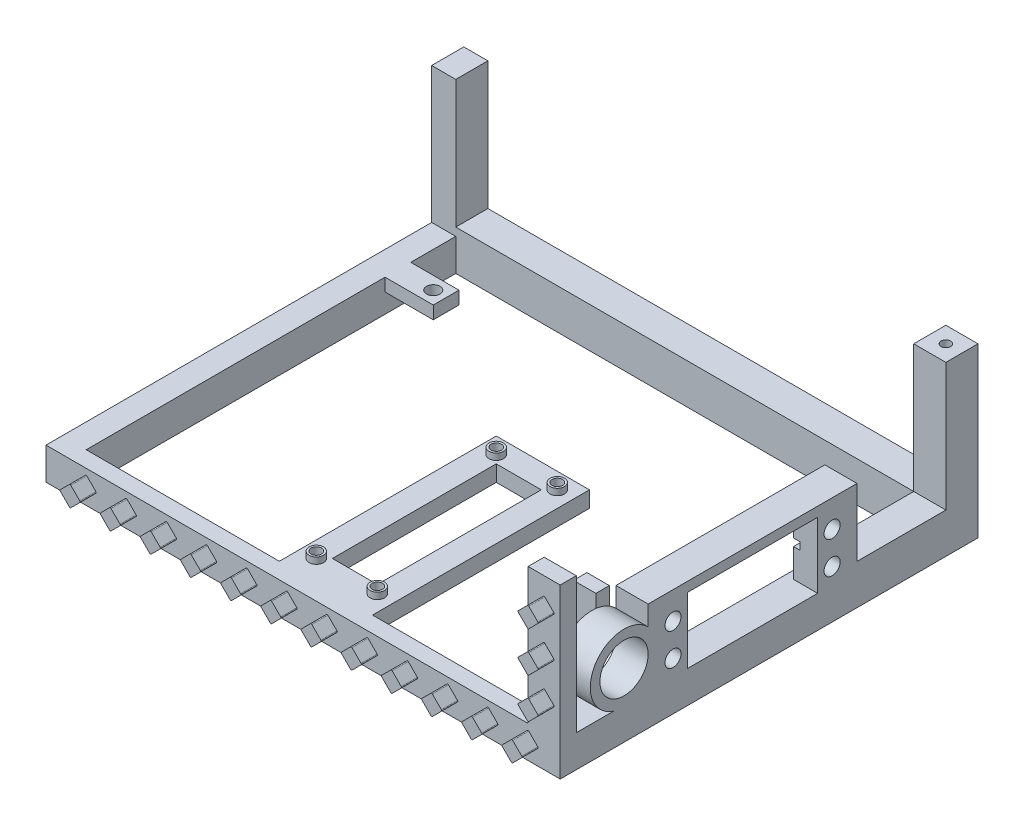
SolidWorks part; units mm, degrees
other "Markup1"
sketch "Sketch27" plane through (-85, 52.3, 65) normal (-0.8972, 0.4289, 0.105) x (0.3802, 0.6295, 0.6776)
ref_plane "Front Plane" through (0, 0, 0) normal (0, 0, 1) x (1, 0, 0)
ref_plane "Top Plane" through (0, 0, 0) normal (0, 1, 0) x (1, 0, 0)
ref_plane "Right Plane" through (0, 0, 0) normal (1, 0, 0) x (0, 0, -1)
sketch "Sketch1" plane through (0, 0, 0) normal (0, 1, 0) x (1, 0, 0)
  line L0 (0, 0) -> (0, 70) construction
  line L1 (-85, -60) -> (75, -60)
  line L2 (-85, -60) -> (-85, 70)
  line L3 (-85, 70) -> (75, 70)
  line L4 (75, -60) -> (75, 70)
  line L5 (0, 0) -> (0, -60) construction
  point P0 (0, 0)
  dimension "D1" = 160
  dimension "D2" = 70
  dimension "D3" = 60
extrude "Boss-Extrude1" add sketch "Sketch1" along normal blind 10
sketch "Sketch2" plane through (0, 10, 0) normal (0, 1, 0) x (1, 0, 0)
  line L0 (-85, 70) -> (75, 70)
  line L4 (-85, 70) -> (-85, 60)
  line L5 (-85, 70) -> (-85, -60) construction
  line L6 (-85, 60) -> (65, 60)
  line L13 (75, 70) -> (75, -60)
  line L14 (75, -60) -> (65, -60)
  line L15 (-85, -60) -> (75, -60) construction
  line L16 (65, -60) -> (65, 60)
extrude "Boss-Extrude2" add sketch "Sketch2" along normal blind 42.3
sketch "Sketch6" plane through (0, 0, 60) normal (0, 0, 1) x (1, 0, 0)
  line L0 (65, 10) -> (75, 10) construction
  line L1 (75, 52.3) -> (75, 0) construction
  line L2 (69.7879, 40.6121) -> (66.9621, 43.4379)
  line L79 (65, 10) -> (65, 0) construction
  line L156 (-85, 0) -> (75, 0) construction
  line L157 (66.9621, 43.8621) -> (69.7879, 46.6879)
  line L158 (70.2121, 46.6879) -> (73.0379, 43.8621)
  line L159 (70, 10) -> (70, 52.3) construction
  line L160 (65, 52.3) -> (75, 52.3) construction
  line L185 (65, 5) -> (-85, 5) construction
  line L186 (-85, 10) -> (-85, 0) construction
  line L187 (-10, 8.25) -> (-10, 1.75) construction
  line L188 (-10.2121, 8.0379) -> (-13.0379, 5.2121)
  line L189 (-13.0379, 4.7879) -> (-10.2121, 1.9621)
  line L190 (-9.7879, 1.9621) -> (-6.9621, 4.7879)
  line L191 (-6.9621, 5.2121) -> (-9.7879, 8.0379)
  line L192 (73.25, 31.15) -> (66.75, 31.15) construction
  line L193 (66.9621, 31.3621) -> (69.7879, 34.1879)
  line L194 (70.2121, 34.1879) -> (73.0379, 31.3621)
  line L195 (73.0379, 30.9379) -> (70.2121, 28.1121)
  line L196 (69.7879, 28.1121) -> (66.9621, 30.9379)
  line L197 (5.5379, 5.2121) -> (2.7121, 8.0379)
  line L198 (2.2879, 8.0379) -> (-0.5379, 5.2121)
  line L199 (-0.5379, 4.7879) -> (2.2879, 1.9621)
  line L200 (2.7121, 1.9621) -> (5.5379, 4.7879)
  line L201 (18.0379, 5.2121) -> (15.2121, 8.0379)
  line L202 (14.7879, 8.0379) -> (11.9621, 5.2121)
  line L203 (11.9621, 4.7879) -> (14.7879, 1.9621)
  line L204 (15.2121, 1.9621) -> (18.0379, 4.7879)
  line L205 (30.5379, 5.2121) -> (27.7121, 8.0379)
  line L206 (27.2879, 8.0379) -> (24.4621, 5.2121)
  line L207 (24.4621, 4.7879) -> (27.2879, 1.9621)
  line L208 (27.7121, 1.9621) -> (30.5379, 4.7879)
  line L209 (43.0379, 5.2121) -> (40.2121, 8.0379)
  line L210 (39.7879, 8.0379) -> (36.9621, 5.2121)
  line L211 (36.9621, 4.7879) -> (39.7879, 1.9621)
  line L212 (40.2121, 1.9621) -> (43.0379, 4.7879)
  line L213 (55.5379, 5.2121) -> (52.7121, 8.0379)
  line L214 (52.2879, 8.0379) -> (49.4621, 5.2121)
  line L215 (49.4621, 4.7879) -> (52.2879, 1.9621)
  line L216 (52.7121, 1.9621) -> (55.5379, 4.7879)
  line L217 (68.0379, 5.2121) -> (65.2121, 8.0379)
  line L218 (64.7879, 8.0379) -> (61.9621, 5.2121)
  line L219 (61.9621, 4.7879) -> (64.7879, 1.9621)
  line L220 (65.2121, 1.9621) -> (68.0379, 4.7879)
  line L221 (-19.4621, 5.2121) -> (-22.2879, 8.0379)
  line L222 (-22.7121, 8.0379) -> (-25.5379, 5.2121)
  line L223 (-25.5379, 4.7879) -> (-22.7121, 1.9621)
  line L224 (-22.2879, 1.9621) -> (-19.4621, 4.7879)
  line L225 (-31.9621, 5.2121) -> (-34.7879, 8.0379)
  line L226 (-35.2121, 8.0379) -> (-38.0379, 5.2121)
  line L227 (-38.0379, 4.7879) -> (-35.2121, 1.9621)
  line L228 (-34.7879, 1.9621) -> (-31.9621, 4.7879)
  line L229 (-44.4621, 5.2121) -> (-47.2879, 8.0379)
  line L230 (-47.7121, 8.0379) -> (-50.5379, 5.2121)
  line L231 (-50.5379, 4.7879) -> (-47.7121, 1.9621)
  line L232 (-47.2879, 1.9621) -> (-44.4621, 4.7879)
  line L233 (-56.9621, 5.2121) -> (-59.7879, 8.0379)
  line L234 (-60.2121, 8.0379) -> (-63.0379, 5.2121)
  line L235 (-63.0379, 4.7879) -> (-60.2121, 1.9621)
  line L236 (-59.7879, 1.9621) -> (-56.9621, 4.7879)
  line L237 (-69.4621, 5.2121) -> (-72.2879, 8.0379)
  line L238 (-72.7121, 8.0379) -> (-75.5379, 5.2121)
  line L239 (-75.5379, 4.7879) -> (-72.7121, 1.9621)
  line L240 (-72.2879, 1.9621) -> (-69.4621, 4.7879)
  line L241 (73.0379, 43.4379) -> (70.2121, 40.6121)
  line L242 (69.7879, 15.6121) -> (66.9621, 18.4379)
  line L243 (66.9621, 18.8621) -> (69.7879, 21.6879)
  line L244 (70.2121, 21.6879) -> (73.0379, 18.8621)
  line L245 (73.0379, 18.4379) -> (70.2121, 15.6121)
  arc A128 (-13.0379, 5.2121) -> (-13.0379, 4.7879) centre (-12.8257, 5) ccw
  arc A129 (-9.7879, 1.9621) -> (-10.2121, 1.9621) centre (-10, 2.1743) cw
  arc A130 (-6.9621, 4.7879) -> (-6.9621, 5.2121) centre (-7.1743, 5) ccw
  arc A131 (-9.7879, 8.0379) -> (-10.2121, 8.0379) centre (-10, 7.8257) ccw
  arc A132 (66.9621, 30.9379) -> (66.9621, 31.3621) centre (67.1743, 31.15) cw
  arc A133 (70.2121, 28.1121) -> (69.7879, 28.1121) centre (70, 28.3243) cw
  arc A134 (73.0379, 30.9379) -> (73.0379, 31.3621) centre (72.8257, 31.15) ccw
  arc A135 (69.7879, 34.1879) -> (70.2121, 34.1879) centre (70, 33.9757) cw
  arc A136 (2.7121, 8.0379) -> (2.2879, 8.0379) centre (2.5, 7.8257) ccw
  arc A137 (5.5379, 4.7879) -> (5.5379, 5.2121) centre (5.3257, 5) ccw
  arc A138 (-0.5379, 5.2121) -> (-0.5379, 4.7879) centre (-0.3257, 5) ccw
  arc A139 (2.7121, 1.9621) -> (2.2879, 1.9621) centre (2.5, 2.1743) cw
  arc A140 (15.2121, 8.0379) -> (14.7879, 8.0379) centre (15, 7.8257) ccw
  arc A141 (18.0379, 4.7879) -> (18.0379, 5.2121) centre (17.8257, 5) ccw
  arc A142 (11.9621, 5.2121) -> (11.9621, 4.7879) centre (12.1743, 5) ccw
  arc A143 (15.2121, 1.9621) -> (14.7879, 1.9621) centre (15, 2.1743) cw
  arc A144 (27.7121, 8.0379) -> (27.2879, 8.0379) centre (27.5, 7.8257) ccw
  arc A145 (30.5379, 4.7879) -> (30.5379, 5.2121) centre (30.3257, 5) ccw
  arc A146 (24.4621, 5.2121) -> (24.4621, 4.7879) centre (24.6743, 5) ccw
  arc A147 (27.7121, 1.9621) -> (27.2879, 1.9621) centre (27.5, 2.1743) cw
  arc A148 (40.2121, 8.0379) -> (39.7879, 8.0379) centre (40, 7.8257) ccw
  arc A149 (43.0379, 4.7879) -> (43.0379, 5.2121) centre (42.8257, 5) ccw
  arc A150 (36.9621, 5.2121) -> (36.9621, 4.7879) centre (37.1743, 5) ccw
  arc A151 (40.2121, 1.9621) -> (39.7879, 1.9621) centre (40, 2.1743) cw
  arc A152 (52.7121, 8.0379) -> (52.2879, 8.0379) centre (52.5, 7.8257) ccw
  arc A153 (55.5379, 4.7879) -> (55.5379, 5.2121) centre (55.3257, 5) ccw
  arc A154 (49.4621, 5.2121) -> (49.4621, 4.7879) centre (49.6743, 5) ccw
  arc A155 (52.7121, 1.9621) -> (52.2879, 1.9621) centre (52.5, 2.1743) cw
  arc A156 (65.2121, 8.0379) -> (64.7879, 8.0379) centre (65, 7.8257) ccw
  arc A157 (68.0379, 4.7879) -> (68.0379, 5.2121) centre (67.8257, 5) ccw
  arc A158 (61.9621, 5.2121) -> (61.9621, 4.7879) centre (62.1743, 5) ccw
  arc A159 (65.2121, 1.9621) -> (64.7879, 1.9621) centre (65, 2.1743) cw
  arc A160 (-22.2879, 8.0379) -> (-22.7121, 8.0379) centre (-22.5, 7.8257) ccw
  arc A161 (-19.4621, 4.7879) -> (-19.4621, 5.2121) centre (-19.6743, 5) ccw
  arc A162 (-25.5379, 5.2121) -> (-25.5379, 4.7879) centre (-25.3257, 5) ccw
  arc A163 (-22.2879, 1.9621) -> (-22.7121, 1.9621) centre (-22.5, 2.1743) cw
  arc A164 (-34.7879, 8.0379) -> (-35.2121, 8.0379) centre (-35, 7.8257) ccw
  arc A165 (-31.9621, 4.7879) -> (-31.9621, 5.2121) centre (-32.1743, 5) ccw
  arc A166 (-38.0379, 5.2121) -> (-38.0379, 4.7879) centre (-37.8257, 5) ccw
  arc A167 (-34.7879, 1.9621) -> (-35.2121, 1.9621) centre (-35, 2.1743) cw
  arc A168 (-47.2879, 8.0379) -> (-47.7121, 8.0379) centre (-47.5, 7.8257) ccw
  arc A169 (-44.4621, 4.7879) -> (-44.4621, 5.2121) centre (-44.6743, 5) ccw
  arc A170 (-50.5379, 5.2121) -> (-50.5379, 4.7879) centre (-50.3257, 5) ccw
  arc A171 (-47.2879, 1.9621) -> (-47.7121, 1.9621) centre (-47.5, 2.1743) cw
  arc A172 (-59.7879, 8.0379) -> (-60.2121, 8.0379) centre (-60, 7.8257) ccw
  arc A173 (-56.9621, 4.7879) -> (-56.9621, 5.2121) centre (-57.1743, 5) ccw
  arc A174 (-63.0379, 5.2121) -> (-63.0379, 4.7879) centre (-62.8257, 5) ccw
  arc A175 (-59.7879, 1.9621) -> (-60.2121, 1.9621) centre (-60, 2.1743) cw
  arc A176 (-72.2879, 8.0379) -> (-72.7121, 8.0379) centre (-72.5, 7.8257) ccw
  arc A177 (-69.4621, 4.7879) -> (-69.4621, 5.2121) centre (-69.6743, 5) ccw
  arc A178 (-75.5379, 5.2121) -> (-75.5379, 4.7879) centre (-75.3257, 5) ccw
  arc A179 (-72.2879, 1.9621) -> (-72.7121, 1.9621) centre (-72.5, 2.1743) cw
  arc A180 (70.2121, 40.6121) -> (69.7879, 40.6121) centre (70, 40.8243) cw
  arc A181 (66.9621, 43.4379) -> (66.9621, 43.8621) centre (67.1743, 43.65) cw
  arc A182 (69.7879, 46.6879) -> (70.2121, 46.6879) centre (70, 46.4757) cw
  arc A183 (73.0379, 43.4379) -> (73.0379, 43.8621) centre (72.8257, 43.65) ccw
  arc A184 (70.2121, 15.6121) -> (69.7879, 15.6121) centre (70, 15.8243) cw
  arc A185 (66.9621, 18.4379) -> (66.9621, 18.8621) centre (67.1743, 18.65) cw
  arc A186 (69.7879, 21.6879) -> (70.2121, 21.6879) centre (70, 21.4757) cw
  arc A187 (73.0379, 18.4379) -> (73.0379, 18.8621) centre (72.8257, 18.65) ccw
  point P19 (-10, 5)
  point P22 (-13.25, 5)
  point P28 (-6.75, 5)
  point P35 (70, 31.15)
  point P42 (70, 27.9)
  point P48 (70, 34.4)
  dimension "D2" = 0.3
  dimension "D1" = 0.3
  dimension "D3" = 2
  dimension "D4" = 2
extrude "Boss-Extrude3" add sketch "Sketch6" along normal blind 5
sketch "Sketch7" plane through (0, 10, 0) normal (0, 1, 0) x (1, 0, 0)
  line L0 (-66.5, 42) -> (-66.5, 60) construction
  line L1 (-85, 60) -> (65, 60) construction
  line L2 (-85, 60) -> (-85, -60) construction
  line L4 (-66.5, 42) -> (-85, 42) construction
  circle A0 centre (-66.5, 42) radius 2.1
  dimension "D1" = 18
  dimension "D3" = 4.2
  dimension "D2" = 18.5
extrude "Cut-Extrude2" cut sketch "Sketch7" against normal through all
sketch "Sketch8" plane through (0, 10, 0) normal (0, 1, 0) x (1, 0, 0)
  line L5 (-77.5, 60) -> (65, 60)
  line L6 (-66.5, 42) -> (-75, 42) construction
  line L7 (-77.5, 46) -> (-62.5, 46)
  line L8 (-62.5, 46) -> (-62.5, 38)
  line L9 (-62.5, 38) -> (-77.5, 38)
  line L11 (-77.5, 60) -> (-77.5, 46)
  line L12 (-85, 60) -> (-85, -60) construction
  line L13 (-77.5, 38) -> (-77.5, -55)
  line L14 (65, 60) -> (65, -55)
  line L15 (65, 60) -> (65, -60) construction
  line L16 (65, -55) -> (-77.5, -55)
  circle A0 centre (-66.5, 42) radius 2.1 construction
  dimension "D3" = 4
  dimension "D2" = 7.5
  dimension "D4" = 4
  dimension "D5" = 4
extrude "Cut-Extrude3" cut sketch "Sketch8" against normal through all contours L13 L16 L14 L5 L11 L7 L8 L9
sketch "Sketch11" plane through (0, 52.3, 0) normal (0, 1, 0) x (1, 0, 0)
  line L0 (75, 70) -> (65, 60) construction
  circle A3 centre (70, 65) radius 1.5
extrude "Cut-Extrude6" cut sketch "Sketch11" against normal blind 4
sketch "Sketch12" plane through (0, 0, -60) normal (0, 0, 1) x (1, 0, 0)
  line L1 (-77.5, 52.3) -> (-77.5, 12.5)
  line L7 (-77.5, 52.3) -> (65, 52.3)
  line L10 (-85, 52.3) -> (65, 52.3) construction
  line L12 (65, 52.3) -> (65, 12.5)
  line L13 (65, 52.3) -> (65, 0) construction
  line L14 (65, 12.5) -> (-77.5, 12.5)
extrude "Cut-Extrude7" cut sketch "Sketch12" against normal through all
sketch "Sketch15" plane through (0, 10, 0) normal (0, 1, 0) x (1, 0, 0)
  line L0 (6.6, 7.5) -> (6.6, -48.5) construction
  line L1 (6.6, 7.5) -> (-12.4, 7.5) construction
  line L2 (6.6, -48.5) -> (-12.4, -48.5) construction
  line L3 (-17.4, 12.5) -> (11.6, 12.5)
  line L4 (11.6, 12.5) -> (11.6, -53.5)
  line L6 (-12.4, -48.5) -> (-12.4, 7.5) construction
  line L9 (11.6, -53.5) -> (-17.4, -53.5)
  line L10 (-17.4, -53.5) -> (-17.4, 12.5)
  line L11 (-12.4, 7.5) -> (6.6, 7.5) construction
  line L23 (-77.5, 38) -> (-77.5, -55) construction
  line L24 (4.1, 5) -> (-9.9, 5)
  line L25 (4.1, 5) -> (4.1, -46)
  line L26 (4.1, -46) -> (-9.9, -46)
  line L27 (-9.9, 5) -> (-9.9, -46)
  line L33 (6.6, -48.5) -> (-12.4, -48.5) construction
  line L35 (6.6, -18.8362) -> (11.6, -18.8362) construction
  line L36 (-12.4, -20.5) -> (-17.4, -20.5) construction
  line L37 (-2.9, -48.5) -> (-2.9, -53.5) construction
  line L42 (-17.4, -53.5) -> (-17.4, -55)
  line L44 (-17.4, -55) -> (11.6, -55)
  line L45 (11.6, -55) -> (11.6, -53.5)
  circle A0 centre (-12.4, 7.5) radius 1.625
  circle A1 centre (6.6, 7.5) radius 1.625
  circle A2 centre (-12.4, -48.5) radius 1.625
  circle A3 centre (6.6, -48.5) radius 1.625
  circle A4 centre (-12.4, 7.5) radius 2.25
  circle A5 centre (6.6, 7.5) radius 2.25
  circle A6 centre (-12.4, -48.5) radius 2.25
  circle A7 centre (6.6, -48.5) radius 2.25
  point P32 (-2.9, -18.8362)
  dimension "D1" = 60.1
  dimension "D6" = 3.25
  dimension "D7" = 3.25
  dimension "D9" = 3.25
  dimension "D10" = 3.25
  dimension "D2" = 5
  dimension "D3" = 1.5
  dimension "D4" = 19
  dimension "D5" = 56
  dimension "D8" = 5
extrude "Boss-Extrude4" add sketch "Sketch15" against normal blind 5 contours L10 L9 A7 A6 A5 A4 L27 L24 L25 L26 | A7 A3 | A6 A2 | A5 A1 | A4 A0 | L45 L9 L42 region at (-2.9, 10, -11.7791) region at (-2.9, 10, 54.25) region at (-14.5864, 10, -7.5) region at (4.4136, 10, -7.5) region at (-14.5864, 10, 48.5) region at (4.4136, 10, 48.5)
extrude "Boss-Extrude5" add sketch "Sketch15<4>" along normal blind 2 contours A6 A2 | A7 A3 | A5 A1 | A4 A0 region at (-14.5864, 10, -7.5) region at (4.4136, 10, -7.5) region at (-14.5864, 10, 48.5) region at (4.4136, 10, 48.5)
sketch "Sketch15<4>" plane through (0, 10, 0) normal (0, 1, 0) x (1, 0, 0) same geometry as "Sketch15"
sketch "Sketch25" plane through (-85, 0, 0) normal (-1, 0, 0) x (0, 0, 1)
  line L0 (60, 5) -> (-60, 5) construction
  line L1 (60, 10) -> (60, 0) construction
  line L2 (-70, 52.3) -> (-70, 0) construction
  line L41 (-60, 10) -> (-70, 10) construction
  line L42 (-65, 10) -> (-65, 52.3) construction
  line L50 (-70, 52.3) -> (-60, 52.3) construction
  line L59 (-60, 10) -> (-60, 0) construction
  line L60 (-70, 0) -> (60, 0) construction
  line L61 (0, 8.425) -> (0, 1.575) construction
  line L62 (0, 8.425) -> (-3.425, 5)
  line L63 (-3.425, 5) -> (0, 1.575)
  line L64 (0, 1.575) -> (3.425, 5)
  line L65 (3.425, 5) -> (0, 8.425)
  line L66 (15.925, 5) -> (12.5, 8.425)
  line L67 (12.5, 8.425) -> (9.075, 5)
  line L68 (9.075, 5) -> (12.5, 1.575)
  line L69 (12.5, 1.575) -> (15.925, 5)
  line L70 (28.425, 5) -> (25, 8.425)
  line L71 (25, 8.425) -> (21.575, 5)
  line L72 (21.575, 5) -> (25, 1.575)
  line L73 (25, 1.575) -> (28.425, 5)
  line L74 (40.925, 5) -> (37.5, 8.425)
  line L75 (37.5, 8.425) -> (34.075, 5)
  line L76 (34.075, 5) -> (37.5, 1.575)
  line L77 (37.5, 1.575) -> (40.925, 5)
  line L78 (53.425, 5) -> (50, 8.425)
  line L79 (50, 8.425) -> (46.575, 5)
  line L80 (46.575, 5) -> (50, 1.575)
  line L81 (50, 1.575) -> (53.425, 5)
  line L82 (-9.075, 5) -> (-12.5, 8.425)
  line L83 (-12.5, 8.425) -> (-15.925, 5)
  line L84 (-15.925, 5) -> (-12.5, 1.575)
  line L85 (-12.5, 1.575) -> (-9.075, 5)
  line L86 (-21.575, 5) -> (-25, 8.425)
  line L87 (-25, 8.425) -> (-28.425, 5)
  line L88 (-28.425, 5) -> (-25, 1.575)
  line L89 (-25, 1.575) -> (-21.575, 5)
  line L90 (-34.075, 5) -> (-37.5, 8.425)
  line L91 (-37.5, 8.425) -> (-40.925, 5)
  line L92 (-40.925, 5) -> (-37.5, 1.575)
  line L93 (-37.5, 1.575) -> (-34.075, 5)
  line L94 (-46.575, 5) -> (-50, 8.425)
  line L95 (-50, 8.425) -> (-53.425, 5)
  line L96 (-53.425, 5) -> (-50, 1.575)
  line L97 (-50, 1.575) -> (-46.575, 5)
  line L98 (-59.075, 5) -> (-62.5, 8.425)
  line L99 (-62.5, 8.425) -> (-65.925, 5)
  line L100 (-65.925, 5) -> (-62.5, 1.575)
  line L101 (-62.5, 1.575) -> (-59.075, 5)
  line L114 (-61.575, 31.15) -> (-68.425, 31.15) construction
  line L115 (-68.425, 31.15) -> (-65, 34.575)
  line L116 (-65, 34.575) -> (-61.575, 31.15)
  line L117 (-61.575, 31.15) -> (-65, 27.725)
  line L118 (-65, 27.725) -> (-68.425, 31.15)
  line L119 (-65, 15.225) -> (-68.425, 18.65)
  line L120 (-68.425, 18.65) -> (-65, 22.075)
  line L121 (-65, 22.075) -> (-61.575, 18.65)
  line L122 (-61.575, 18.65) -> (-65, 15.225)
  line L123 (-65, 40.225) -> (-68.425, 43.65)
  line L124 (-68.425, 43.65) -> (-65, 47.075)
  line L125 (-65, 47.075) -> (-61.575, 43.65)
  line L126 (-61.575, 43.65) -> (-65, 40.225)
  point P10 (0, 5)
  point P54 (-65, 31.15)
  dimension "D1" = 5
  dimension "D3" = 2
  dimension "D2" = 6
  dimension "D4" = 2
extrude "Cut-Extrude20" cut sketch "Sketch25" against normal blind 5.25
sketch "Sketch26" plane through (0, 0, 0) normal (0, -1, 0) x (1, 0, 0)
  line L0 (-77.5, -46) -> (-77.5, -38)
  line L1 (-77.5, -38) -> (-62.5, -38)
  line L2 (-62.5, -38) -> (-62.5, -46)
  line L3 (-62.5, -46) -> (-77.5, -46)
extrude "Cut-Extrude21" cut sketch "Sketch26" against normal blind 6
sketch "Sketch36" plane through (65, 0, 0) normal (-1, 0, 0) x (0, 0, 1)
  line L0 (-27.35, 30.5) -> (-27.35, 10)
  line L1 (-27.35, 30.5) -> (27.65, 30.5)
  line L2 (-27.35, 10) -> (27.65, 10)
  line L3 (27.65, 10) -> (27.65, 30.5)
  line L7 (-70, 52.3) -> (60, 52.3) construction
  line L8 (-70, 12.5) -> (-70, 52.3) construction
  dimension "D1" = 21.8
  dimension "D3" = 42.65
  dimension "D4" = 20.5
extrude "Cut-Extrude27" cut sketch "Sketch36" against normal blind 2.5
sketch "Sketch37" plane through (67.5, 0, 0) normal (-1, 0, 0) x (0, 0, 1)
  line L0 (-20.1, 18.85) -> (-27.35, 18.85)
  line L1 (-27.35, 18.85) -> (-27.35, 21.15)
  line L2 (-27.35, 21.15) -> (-20.1, 21.15)
  line L4 (-20.1, 18.85) -> (-20.1, 21.15)
  line L6 (27.65, 30.5) -> (-27.35, 30.5) construction
  dimension "D1" = 9.35
extrude "Cut-Extrude28" cut sketch "Sketch37" against normal blind 2
sketch "Sketch38" plane through (67.5, 0, 0) normal (-1, 0, 0) x (0, 0, 1)
  line L4 (27.65, 30.5) -> (-27.35, 30.5) construction
  line L5 (-27.35, 30.5) -> (-27.35, 21.15) construction
  circle A0 centre (-24.6, 25) radius 2.5
  circle A1 centre (-24.6, 15) radius 2.5
  dimension "D4" = 5
  dimension "D1" = 5.5
  dimension "D2" = 10
  dimension "D3" = 2.75
sketch "Sketch39" plane through (65, 0, 0) normal (-1, 0, 0) x (0, 0, 1)
  line L0 (-60, 52.3) -> (-60, 12.5)
  line L1 (-60, 12.5) -> (-32.35, 12.5)
  line L2 (-32.35, 12.5) -> (-32.35, 33.5)
  line L3 (-32.35, 33.5) -> (55, 33.5)
  line L5 (-60, 52.3) -> (55, 52.3)
  line L6 (55, 52.3) -> (55, 33.5)
  line L7 (60, 52.3) -> (60, 10) construction
  dimension "D1" = 5
  dimension "D2" = 21
extrude "Cut-Extrude30" cut sketch "Sketch39" against normal blind 10
sketch "Sketch40" plane through (65, 0, 0) normal (-1, 0, 0) x (0, 0, 1)
  line L5 (55, 33.5) -> (32.65, 33.5)
  line L6 (-32.35, 33.5) -> (55, 33.5) construction
  line L7 (32.65, 33.5) -> (32.65, 10)
  line L8 (32.65, 10) -> (55, 10)
  line L9 (55, 33.5) -> (55, 10)
  circle A0 centre (40.15, 20) radius 7.5
  arc A1 (32.65, 12.6515) -> (36.9484, 10) centre (40.15, 20) ccw
  arc A2 (43.3516, 10) -> (32.65, 27.3485) centre (40.15, 20) ccw
  line M7 (55, 33.5) -> (-32.35, 33.5)
extrude "Cut-Extrude32" cut sketch "Sketch40" against normal blind 10 contours A2 L8 L9 L7 M7 | A0 region at (65, 21.75, 54.6757) region at (65, 20, 40.15)
sketch "Sketch41" plane through (67.5, 0, 0) normal (-1, 0, 0) x (0, 0, 1)
  line L0 (-20.1, 30.5) -> (20.4, 30.5)
  line L1 (20.4, 30.5) -> (20.4, 10)
  line L2 (20.4, 10) -> (-20.1, 10)
  line L3 (-20.1, 10) -> (-20.1, 30.5)
  line L5 (-32.35, 12.5) -> (-32.35, 33.5) construction
  line L6 (32.65, 33.5) -> (32.65, 27.3485) construction
  dimension "D1" = 12.25
  dimension "D2" = 12.25
extrude "Cut-Extrude33" cut sketch "Sketch38" against normal blind 10
extrude "Cut-Extrude34" cut sketch "Sketch41" against normal blind 10
ref_plane "Plane2" through (0, 0, 0.15) normal (0, 0, 1) x (1, 0, 0)
mirror "Mirror1" about plane through (0, 0, 0.15) normal (0, 0, 1) of "Cut-Extrude28", "Cut-Extrude33"
sketch "Sketch48" plane through (65, 0, 0) normal (-1, 0, 0) x (0, 0, 1)
  line L0 (24.4, 10) -> (20.2, 10)
  line L1 (20.2, 10) -> (20.2, 7)
  line L2 (20.2, 7) -> (24.4, 7)
  line L3 (24.4, 7) -> (24.4, 10)
  line L4 (-27.35, 10) -> (27.65, 10) construction
  dimension "D1" = 4.2
extrude "Boss-Extrude9" add sketch "Sketch48" along normal blind 21.5
sketch "Sketch49" plane through (0, 10, 0) normal (0, 1, 0) x (1, 0, 0)
  line L0 (43.5, -24.4) -> (43.5, -20.2)
  line L1 (43.5, -20.2) -> (50.5, -20.2)
  line L2 (43.5, -20.2) -> (65, -20.2) construction
  line L3 (50.5, -20.2) -> (50.5, -24.4)
  line L4 (43.5, -24.4) -> (65, -24.4) construction
  line L5 (50.5, -24.4) -> (43.5, -24.4)
extrude "Boss-Extrude10" add sketch "Sketch49" along normal blind 10
